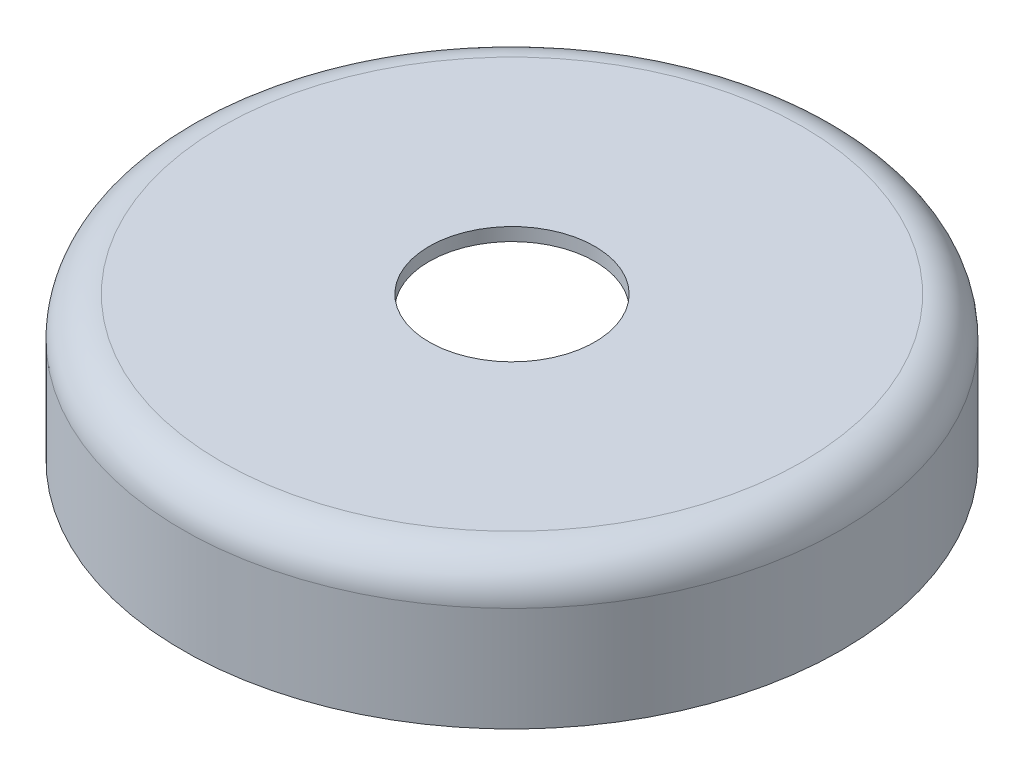
SolidWorks part; units mm, degrees
ref_plane "Front Plane" through (0, 0, 0) normal (0, 0, 1) x (1, 0, 0)
ref_plane "Top Plane" through (0, 0, 0) normal (0, 1, 0) x (1, 0, 0)
ref_plane "Right Plane" through (0, 0, 0) normal (1, 0, 0) x (0, 0, -1)
sketch "Sketch1" plane through (0, 0, 0) normal (0, 0, 1) x (1, 0, 0)
  line L0 (0, 10) -> (0, 0) construction
  line L1 (6.35, 11) -> (0, 11) construction
  line L2 (6.35, 10) -> (23.5, 10)
  line L3 (6.35, 10) -> (6.35, 11)
  line L4 (6.35, 11) -> (23.5, 11)
  line L5 (23.5, 10) -> (23.5, 11)
  line L6 (23.5, 11) -> (25.25, 11)
  line L7 (23.5, 11) -> (23.5, 0)
  line L8 (23.5, 0) -> (25.25, 0)
  line L9 (25.25, 11) -> (25.25, 0)
  line L10 (6.35, 11) -> (6.35, 10) construction
  line L11 (6.35, 10) -> (0, 10) construction
  line L12 (0, 11) -> (0, 10) construction
  point P9 (24.375, 0)
  dimension "D1" = 1.75
  dimension "D2" = 6.35
  dimension "D3" = 1
  dimension "D4" = 10
  dimension "D5" = 23.5
revolve "Revolve1" add sketch "Sketch1" angle 360 about L0
thread "Thread1" pitch 2.5 method cut trim with start face yes profile "Thread Profile1" start angle 0, offset 2.5, length 0, pitch 2.5, diameter 47
ref_plane "Plane1" through (23.5, -2.5, 0) normal (0, 0, 1) x (1, 0, 0)
sketch "Thread Profile1" plane through (23.5, -2.5, 0) normal (0, 0, 1) x (1, 0, 0)
  line L0 (0, 0) -> (0, 2.5) construction
  line L1 (0, 0) -> (1.3532, 0.7812)
  line L2 (1.3532, 0.7812) -> (1.3532, 1.0937)
  line L3 (1.3532, 1.0937) -> (0, 1.875)
  line L4 (1.3532, 0.9375) -> (0, 0.9375) construction
  line L11 (0, 0) -> (0, 1.875)
  point P2 (0, 0)
  dimension "Pitch" = 2.5
  dimension "Profile_Angle" = 60
  dimension "Profile_Land" = 0.3125
  dimension "Profile_Height" = 1.3532
fillet "Fillet1" radius 3 1 edges at (-25.25, 11, 0)
